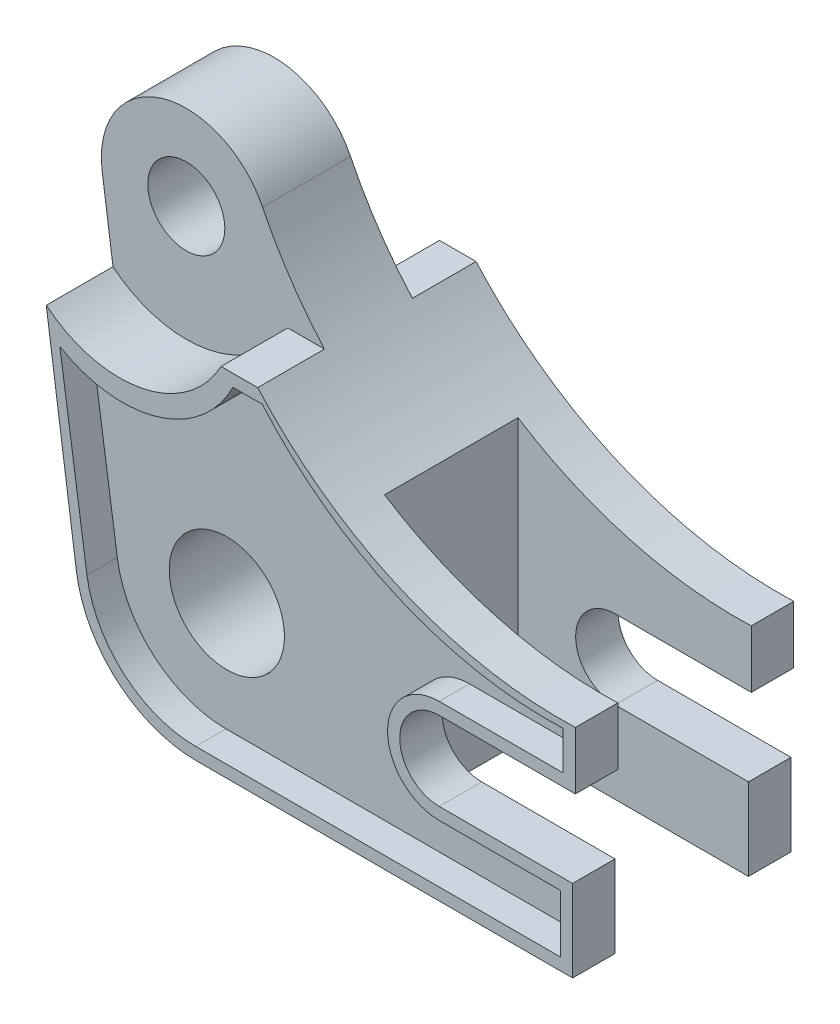
SolidWorks part; units mm, degrees
material "AISI 1020 Steel, Cold Rolled"
ref_plane "Front Plane" through (0, 0, 0) normal (0, 0, 1) x (1, 0, 0)
ref_plane "Top Plane" through (0, 0, 0) normal (0, 1, 0) x (1, 0, 0)
ref_plane "Right Plane" through (0, 0, 0) normal (1, 0, 0) x (0, 0, -1)
sketch "Sketch1" plane through (0, 0, 0) normal (0, 0, 1) x (1, 0, 0)
  line L0 (0, -72.6333) -> (0, 72.6333) construction
  line L1 (-62, 0) -> (62, 0) construction
  line L2 (0, -20) -> (62, -20)
  line L3 (40, -6.5) -> (62, -6.5)
  line L4 (62, -6.5) -> (62, -20)
  line L5 (40, 6.5) -> (62.4539, 6.5)
  line L6 (62.4539, 6.5) -> (62.4539, 15.9971)
  line L8 (-19.807, -2.7719) -> (-26.547, 45.39)
  line L9 (0, 0) -> (-12.6821, 47.3304) construction
  line L10 (0, -9.5) -> (0, 9.5) construction
  arc A1 (40, 6.5) -> (40, -6.5) centre (40, 0) ccw
  circle A2 centre (0, 0) radius 9.5
  circle A3 centre (-12.6821, 47.3304) radius 6.35
  arc A4 (-19.807, -2.7719) -> (0, -20) centre (0, 0) ccw
  arc A7 (46.5, 0) -> (40, 6.5) centre (40, 0) ccw construction
  arc A8 (40, -6.5) -> (46.5, 0) centre (40, 0) ccw construction
  arc A9 (62.4539, 15.9971) -> (-0.1088, 53.4876) centre (60.0635, 82.9545) cw
  arc A10 (-26.547, 45.39) -> (-0.1088, 53.4876) centre (-12.6821, 47.3304) cw
  point P4 (0, 0)
  point P8 (0, 0)
  point P21 (0, 0)
  point P27 (0, 0)
  dimension "D1" = 20
  dimension "D2" = 13
  dimension "D7" = 19
  dimension "D8" = 15
  dimension "D10" = 12.7
  dimension "D11" = 14
  dimension "D12" = 9.4971
  dimension "D6" = 67
  dimension "D3" = 62
  dimension "D4" = 22
  dimension "D5" = 36
  dimension "D9" = 49
extrude "Boss-Extrude2" add sketch "Sketch1" along normal blind 26.5
sketch "Sketch2" plane through (0, 0, 26.5) normal (0, 0, 1) x (1, 0, 0)
  line L0 (-26.547, 45.39) -> (-19.807, -2.7719) construction
  line L1 (4.0511, 38.3304) -> (10.0866, 38.3304)
  arc A0 (-24.7667, 32.6688) -> (4.0511, 38.3304) centre (-12.6821, 47.3304) ccw
  arc A1 (-0.1088, 53.4876) -> (62.4539, 15.9971) centre (60.0635, 82.9545) ccw construction
  dimension "D1" = 19
  dimension "D2" = 9
extrude "Cut-Extrude1" cut sketch "Sketch2" against normal blind 6 and the other way through all
sketch "Sketch3" plane through (0, 0, 0) normal (0, 0, -1) x (-1, 0, 0)
  line L0 (26.547, 45.39) -> (19.807, -2.7719) construction
  line L1 (-4.0511, 38.3304) -> (-10.0866, 38.3304)
  line L2 (24.7667, 32.6688) -> (26.547, 45.39)
  arc A0 (24.7667, 32.6688) -> (-4.0511, 38.3304) centre (12.6821, 47.3304) cw
  arc A1 (-62.4539, 15.9971) -> (0.1088, 53.4876) centre (-60.0635, 82.9545) ccw construction
  arc A2 (26.547, 45.39) -> (0.1088, 53.4876) centre (12.6821, 47.3304) ccw
  arc A3 (0.1088, 53.4876) -> (-10.0866, 38.3304) centre (-60.0635, 82.9545) cw
  dimension "D1" = 19
  dimension "D2" = 9
extrude "Cut-Extrude3" cut sketch "Sketch3" against normal blind 6
sketch "Sketch4" plane through (62, 0, 0) normal (1, 0, 0) x (0, 0, -1)
  line L0 (-26.5, -20) -> (0, -20) construction
  line L1 (-19.5, -20) -> (-7, -20)
  line L2 (-19.5, -20) -> (-19.5, 28)
  line L3 (-19.5, 28) -> (-7, 28)
  line L4 (-7, -20) -> (-7, 28)
  line L7 (0, -20) -> (0, -6.5) construction
  line L8 (-26.5, -20) -> (-26.5, -6.5) construction
  dimension "D1" = 48
  dimension "D2" = 7
  dimension "D3" = 7
extrude "Cut-Extrude6" cut sketch "Sketch4" against normal blind 38
sketch "Sketch6" plane through (62.4539, 0, 0) normal (1, 0, 0) x (0, 0, -1)
  line L0 (-26.5, 15.9971) -> (0, 15.9971) construction
  line L1 (-19.5, 6.5) -> (-7.0044, 6.5)
  line L2 (-19.5, 6.5) -> (-19.5, 15.9971)
  line L3 (-19.5, 15.9971) -> (-7.0044, 15.9971)
  line L4 (-7.0044, 6.5) -> (-7.0044, 15.9971)
  line L5 (0, 6.5) -> (0, 15.9971) construction
  dimension "D1" = 7.0044
extrude "Cut-Extrude7" cut sketch "Sketch6" against normal blind 38
sketch "Sketch7" plane through (0, 0, 26.5) normal (0, 0, 1) x (1, 0, 0)
  line L0 (60, -18) -> (-0.1235, -18)
  line L1 (0, -20) -> (62, -20) construction
  line L2 (60, -18) -> (60, -8.5)
  line L3 (60, -8.5) -> (40, -8.5)
  line L4 (62, -6.5) -> (40, -6.5) construction
  line L5 (62, -20) -> (62, -6.5) construction
  line L6 (-0.1235, -18) -> (-0.1235, 18.0004) construction
  line L7 (-18.0547, -2.512) -> (-22.5242, 27.8913)
  line L8 (10.8408, 36.3304) -> (6.0047, 36.3304)
  line L9 (62.4539, 6.5) -> (62.4539, 15.9971) construction
  line L10 (-24.7667, 32.6688) -> (-19.807, -2.7719) construction
  line L11 (40, 8.5) -> (60.4539, 8.5)
  line L12 (60.4539, 8.5) -> (60.4539, 14.863)
  line L13 (4.0511, 38.3304) -> (10.0866, 38.3304) construction
  line L14 (62.4539, 15.9971) -> (62.4539, 6.5)
  line L15 (62.4539, 6.5) -> (40, 6.5)
  line L16 (62, -6.5) -> (40, -6.5)
  line L17 (62, -6.5) -> (62, -20)
  line L18 (62, -20) -> (0, -20)
  line L19 (-24.7667, 32.6688) -> (-19.807, -2.7719)
  line L20 (10.0866, 38.3304) -> (4.0511, 38.3304)
  arc A1 (-0.1235, -18) -> (-18.0547, -2.512) centre (-0.1235, 0.1239) cw
  arc A2 (-19.807, -2.7719) -> (0, -20) centre (0, 0) ccw construction
  arc A3 (40, 8.5) -> (40, -8.5) centre (40, 0) ccw
  arc A4 (40, 6.5) -> (40, -6.5) centre (40, 0) ccw construction
  arc A5 (60.4539, 14.863) -> (10.8408, 36.3304) centre (58.0196, 77.3011) cw
  arc A6 (6.0047, 36.3304) -> (-22.5242, 27.8913) centre (-12.1885, 45.3922) cw
  arc A7 (10.0866, 38.3304) -> (62.4539, 15.9971) centre (60.0635, 82.9545) ccw construction
  arc A8 (-24.7667, 32.6688) -> (4.0511, 38.3304) centre (-12.6821, 47.3304) ccw construction
  arc A9 (-19.807, -2.7719) -> (0, -20) centre (0, 0) ccw
  arc A10 (40, 6.5) -> (40, -6.5) centre (40, 0) ccw
  arc A11 (4.0511, 38.3304) -> (-24.7667, 32.6688) centre (-12.6821, 47.3304) cw
  arc A13 (10.0866, 38.3304) -> (62.4539, 15.9971) centre (60.0635, 82.9545) ccw
  point P15 (-0.1235, 0.0002)
  point P26 (40, 0)
  dimension "D4" = 0.175
  dimension "D5" = 2
  dimension "D6" = 8.5
  dimension "D7" = 18.1239
  dimension "D9" = 20.3251
  dimension "D11" = 62.4855
  dimension "D14" = 6.0115
  dimension "D16" = 2
  dimension "D17" = 2
  dimension "D18" = 67
  dimension "D1" = 2
  dimension "D2" = 2
  dimension "D3" = 2
  dimension "D8" = 0.396
  dimension "D10" = 4.8361
  dimension "D12" = 6.363
  dimension "D13" = 2
  dimension "D15" = 2
extrude "Boss-Extrude3" add sketch "Sketch7" along normal blind 5 and the other way blind 31
sketch "Sketch9" plane through (62, 0, 0) normal (1, 0, 0) x (0, 0, -1)
  line L0 (-31.5, -20) -> (4.5, -20) construction
  line L1 (-24.5, -20) -> (-2.5, -20)
  line L2 (-24.5, -20) -> (-24.5, 28)
  line L3 (-24.5, 28) -> (-2.5, 28)
  line L4 (-2.5, -20) -> (-2.5, 28)
  line L5 (4.5, 6.5) -> (4.5, 15.9971) construction
  line L6 (-31.5, 6.5) -> (-31.5, 15.9971) construction
  dimension "D1" = 7
  dimension "D2" = 7
  dimension "D3" = 48
extrude "Cut-Extrude8" cut sketch "Sketch9" against normal blind 38
sketch "Sketch10" plane through (62.4539, 0, 0) normal (1, 0, 0) x (0, 0, -1)
  line L0 (-31.5, 15.9971) -> (4.5, 15.9971) construction
  line L1 (-24.5, 6.5) -> (-2.5, 6.5)
  line L2 (-24.5, 6.5) -> (-24.5, 15.9971)
  line L3 (-24.5, 15.9971) -> (-2.5, 15.9971)
  line L4 (-2.5, 6.5) -> (-2.5, 15.9971)
  line L5 (4.5, 6.5) -> (4.5, 15.9971) construction
  dimension "D1" = 7
extrude "Cut-Extrude9" cut sketch "Sketch10" against normal blind 38
